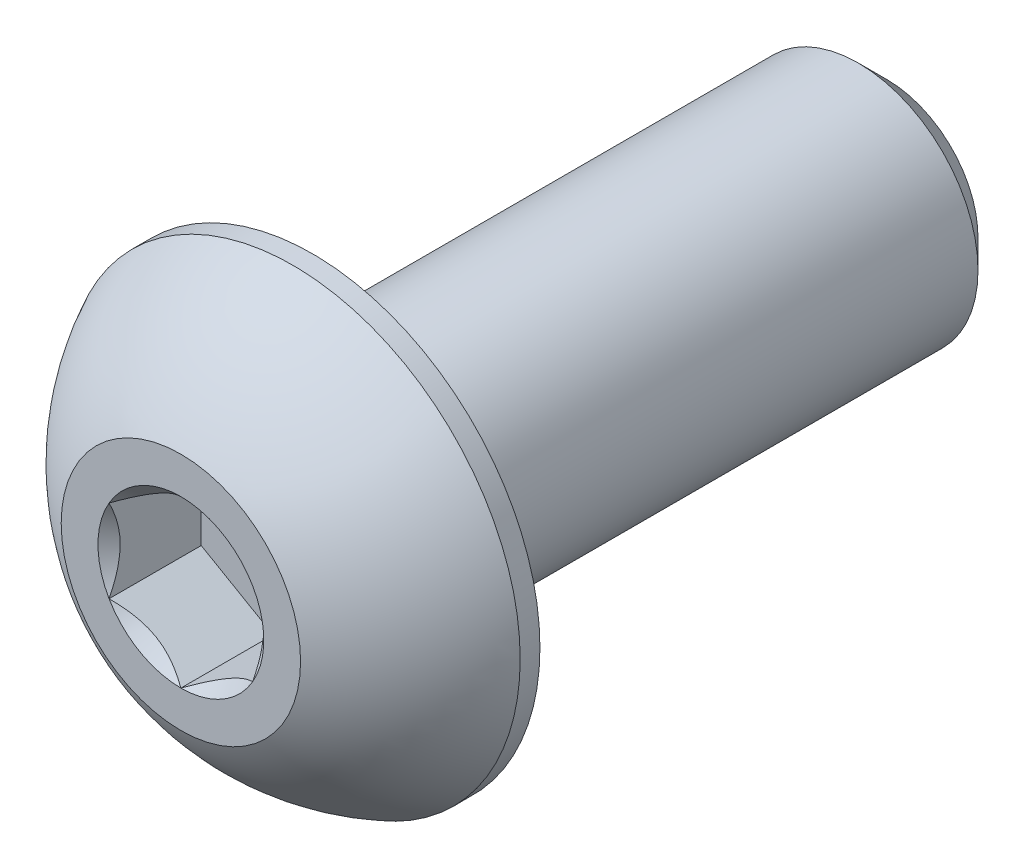
SolidWorks part; units mm, degrees
ref_plane "Front" through (0, 0, 0) normal (0, 0, 1) x (1, 0, 0)
ref_plane "Top" through (0, 0, 0) normal (0, 1, 0) x (1, 0, 0)
ref_plane "Right" through (0, 0, 0) normal (1, 0, 0) x (0, 0, -1)
sketch "Sketch1" plane through (0, 0, 0) normal (1, 0, 0) x (0, 0, -1)
  line L2 (2.75, 2.5) -> (14.75, 2.5)
  line L3 (14.75, 2.5) -> (14.75, 0)
  line L4 (14.75, 0) -> (2.75, 0)
  line L6 (2.3375, 4.75) -> (2.75, 4.75) construction
  line L7 (14.75, 2.5) -> (14.75, -2.5) construction
  line L8 (0, 0) -> (2.75, 0) construction
  line L9 (2.75, 4.75) -> (2.75, -4.75) construction
  line L11 (2.75, 2.5) -> (2.75, 0)
  line L13 (0, 1.5) -> (0, -1.5) construction
  line L14 (0, 1.5) -> (0, 2.5) construction
  arc A3 (0, 2.5) -> (2.3375, 4.75) centre (4.6581, 0) cw construction
  dimension "D1" = 0.4125
revolve "Revolve1" add sketch "Sketch1" angle 360 mid plane about L4
sketch "Sketch3" plane through (0, 0, -14.75) normal (0, 0, -1) x (-1, 0, 0)
  circle A0 centre (0, 0) radius 2.5
curve "Helix/Spiral1" pitch 0.8 height 12.8 turns 16
sketch "Sketch2" plane through (0, 0, 0) normal (1, 0, 0) x (0, 0, -1)
  line L0 (14.75, 2.5) -> (15.45, 2.5)
  line L1 (15.45, 2.5) -> (15.15, 1.9804)
  line L2 (15.15, 1.9804) -> (15.05, 1.9804)
  line L3 (15.05, 1.9804) -> (14.75, 2.5)
  line L4 (14.9, 2.2402) -> (15.3, 2.2402) construction
  dimension "D1" = 60
  dimension "D2" = 0.1
  dimension "D3" = 0.4
chamfer "Chamfer1" distance 0.6 angle 45 1 edges at (0, 2.5, -14.75)
sweep "Cut-Sweep1" [suppressed] cut profiles "Sketch2" path "Helix/Spiral1"
sketch "Sketch7" plane through (0, 0, 0) normal (1, 0, 0) x (0, 0, -1)
  line L6 (2.3375, 4.75) -> (2.75, 4.75) construction
  line L8 (0, 0) -> (2.75, 0) construction
  line L11 (2.75, 4.75) -> (2.75, -4.75) construction
  line L12 (2.3375, 4.75) -> (2.75, 4.75)
  line L13 (0, 0) -> (2.75, 0)
  line L14 (0, 1.5) -> (0, -1.5) construction
  line L15 (2.75, 4.75) -> (2.75, 0)
  line L16 (0, 2.5) -> (0, 0)
  arc A2 (2.3375, 4.75) -> (0, 2.5) centre (4.6581, 0) ccw construction
  arc A3 (2.3375, 4.75) -> (0, 2.5) centre (4.6581, 0) ccw
revolve "Revolve2" add sketch "Sketch7" angle 360 mid plane about L13
sketch "Sketch5" plane through (0, 0, 0) normal (0, 0, 1) x (1, 0, 0)
  line L1 (1.5, -0.866) -> (1.5, 0.866)
  line L2 (1.5, 0.866) -> (0, 1.7321)
  line L3 (0, 1.7321) -> (-1.5, 0.866)
  line L4 (-1.5, 0.866) -> (-1.5, -0.866)
  line L5 (-1.5, -0.866) -> (0, -1.7321)
  line L6 (0, -1.7321) -> (1.5, -0.866)
  circle A0 centre (0, 0) radius 1.5 construction
extrude "Cut-Extrude2" cut sketch "Sketch5" against normal blind 1.925
sketch "Sketch6" plane through (0, 0, 0) normal (0, 0, 1) x (1, 0, 0)
  circle A0 centre (0, 0) radius 1.7321
extrude "Cut-Extrude3" cut sketch "Sketch6" against normal blind 1.925 draft 45
sketch "Sketch9" [suppressed] plane through (0, 0, -2.75) normal (0, 0, 1) x (1, 0, 0)
  circle A2 centre (0, 0) radius 2.5
extrude "Boss-Extrude2" [suppressed] add sketch "Sketch9" against normal offset from surface (13 mm away) 20
sketch "Sketch10" plane through (0, 0, 0) normal (1, 0, 0) x (0, 0, -1)
  line L0 (14.75, 2.5) -> (14.75, -2.5) construction
  point P0 (13.55, -2.5)
  dimension "D1" = 1.2
ref_axis "Axis1" through (0, 0, -2.75) along (0, 0, -1)
equation "\"D3@Helix/Spiral1\" = \"Lg@Sketch1\" + \"D4@Helix/Spiral1\""
equation "\"D2@Sketch2\" = \"D4@Helix/Spiral1\" * .125"
equation "\"D3@Sketch2\" = \"D4@Helix/Spiral1\" * .5"
equation "\"D1@Chamfer1\" = \"D4@Helix/Spiral1\" * .75"
equation "\"D1@Cut-Extrude2\" = \"Head Ht@Sketch1\" * .7"
equation "\"D1@Sketch1\" = \"Head Ht@Sketch1\" * .15"
equation "\"D1@Sketch10\" = \"D4@Helix/Spiral1\" * 1.5"
equation "\"D1@Cut-Extrude3\" = \"D1@Cut-Extrude2\""
